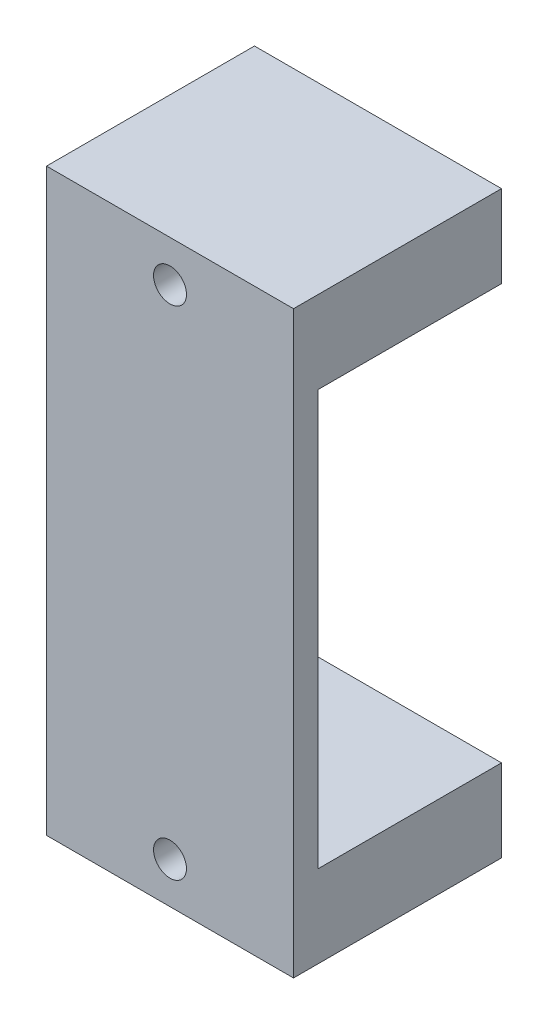
SolidWorks part; units mm, degrees
ref_plane "Front Plane" through (0, 0, 0) normal (0, 0, 1) x (1, 0, 0)
ref_plane "Top Plane" through (0, 0, 0) normal (0, 1, 0) x (1, 0, 0)
ref_plane "Right Plane" through (0, 0, 0) normal (1, 0, 0) x (0, 0, -1)
sketch "Sketch2" plane through (0, 0, 0) normal (0, 0, 1) x (1, 0, 0)
  line L0 (69, -22) -> (-75.5, -22) construction
  line L1 (-37.5, -32) -> (-7.5, -32)
  line L2 (-37.5, -32) -> (-37.5, 38.4)
  line L3 (-37.5, 38.4) -> (-7.5, 38.4)
  line L4 (-7.5, -32) -> (-7.5, 38.4)
  line L5 (-37.5, -32) -> (-7.5, 38.4) construction
  line L6 (-37.5, 38.4) -> (-7.5, -32) construction
  line L7 (-75.5, 28.4) -> (69, 28.4) construction
  line L8 (-75.5, -22) -> (-75.5, 28.4) construction
  line L9 (-37.5, -22) -> (-7.5, -22) construction
  line L10 (-7.5, -22) -> (-7.5, 28.4) construction
  line L11 (-7.5, 28.4) -> (-37.5, 28.4) construction
  line L12 (-22.5, -32) -> (-22.5, -22) construction
  line L14 (-22.5, 28.4) -> (-22.5, 38.4) construction
  circle A0 centre (-22.5, -27) radius 2
  circle A1 centre (-22.5, 33.4) radius 2
  point P4 (-22.5, 3.2)
  line M7 (69, 28.4) -> (-75.5, 28.4)
  line M9 (-75.5, -22) -> (69, -22)
  dimension "D5" = 4
  dimension "D6" = 4
  dimension "D1" = 10
  dimension "D2" = 10
  dimension "D3" = 38
  dimension "D4" = 30
extrude "Boss-Extrude1" add sketch "Sketch2" along normal blind 3
extrude "Boss-Extrude2" add sketch "Sketch2<2>" against normal up to surface (22.26 mm away) contours L1 L4 L2 A0 M9 | L4 L3 L2 A1 M7 region at (-37.1838, -27, 0) region at (-37.1838, 33.4, 0)
sketch "Sketch2<2>" plane through (0, 0, 0) normal (0, 0, 1) x (1, 0, 0) same geometry as "Sketch2"
